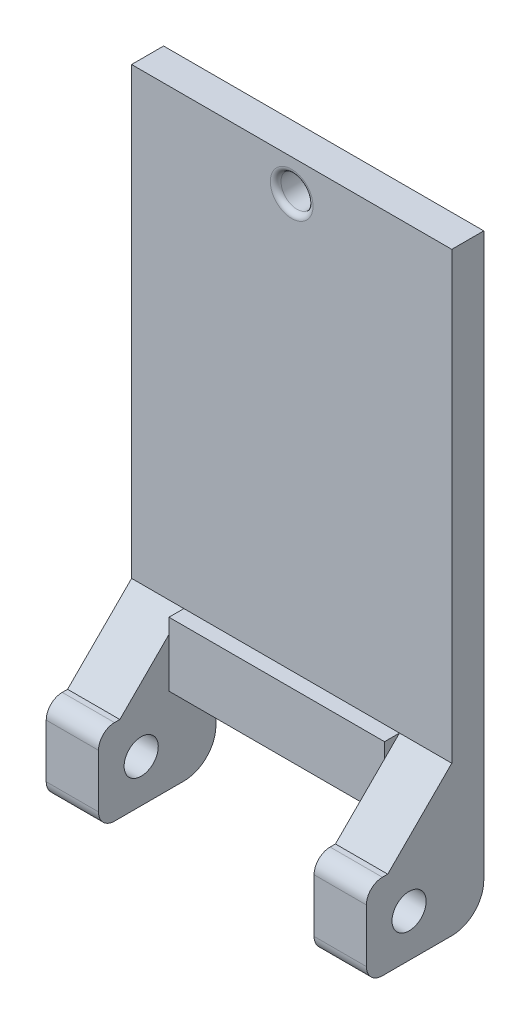
SolidWorks part; units mm, degrees
ref_plane "Front Plane" through (0, 0, 0) normal (0, 0, 1) x (1, 0, 0)
ref_plane "Top Plane" through (0, 0, 0) normal (0, 1, 0) x (1, 0, 0)
ref_plane "Right Plane" through (0, 0, 0) normal (1, 0, 0) x (0, 0, -1)
sketch "Sketch1" plane through (0, 0, 0) normal (0, 0, 1) x (1, 0, 0)
  line L1 (-15, -27.85) -> (15, -27.85)
  line L2 (-15, -27.85) -> (-15, 27.85)
  line L3 (-15, 27.85) -> (15, 27.85)
  line L4 (15, -27.85) -> (15, 27.85)
  line L5 (-15, -27.85) -> (15, 27.85) construction
  line L6 (-15, 27.85) -> (15, -27.85) construction
  point P0 (0, 0)
  dimension "D1" = 55.7
  dimension "D2" = 30
extrude "Boss-Extrude1" add sketch "Sketch1" along normal blind 3
sketch "Sketch2" plane through (0, 0, 3) normal (0, 0, 1) x (1, 0, 0)
  line L0 (0, -27.85) -> (0, 27.85) construction
  line L1 (15, 27.85) -> (-15, 27.85) construction
  line L3 (-15, -27.85) -> (-10.1, -27.85)
  line L4 (-15, -27.85) -> (-15, -19.85)
  line L5 (-15, -19.85) -> (-10.1, -19.85)
  line L6 (-10.1, -27.85) -> (-10.1, -19.85)
  point P6 (0, 0)
  dimension "D1" = 4.9
  dimension "D2" = 8
extrude "Boss-Extrude2" add sketch "Sketch2" along normal blind 8
sketch "Sketch3" plane through (-15, 0, 0) normal (-1, 0, 0) x (0, 0, 1)
  line L0 (11, -27.85) -> (0, -27.85) construction
  line L2 (3, 27.85) -> (3, -19.85) construction
  circle A0 centre (7, -23.85) radius 1.6
  dimension "D1" = 3.2
  dimension "D2" = 4
  dimension "D3" = 4
extrude "Cut-Extrude1" cut sketch "Sketch3" against normal through all
mirror "Mirror1" about plane through (0, 0, 0) normal (1, 0, 0) of "Cut-Extrude1", "Boss-Extrude2"
sketch "Sketch4" plane through (0, 0, 3) normal (0, 0, 1) x (1, 0, 0)
  line L1 (15, 27.85) -> (-15, 27.85) construction
  line L3 (0, 27.85) -> (0, 24.85) construction
  circle A0 centre (0, 24.85) radius 1.5
  dimension "D1" = 3
  dimension "D2" = 3
extrude "Cut-Extrude2" cut sketch "Sketch4" against normal blind 10 contours A0
fillet "Fillet3" radius 0.5 2 edges at (-1.5, 24.85, 0) (1.5, 24.85, 3)
fillet "Fillet4" radius 3 1 edges at (0, -27.85, 0)
sketch "Sketch5" plane through (0, 0, 3) normal (0, 0, 1) x (1, 0, 0)
  line L0 (10.1, -27.85) -> (10.1, -19.85) construction
  line L1 (-10.1, -27.85) -> (-10.1, -19.85) construction
  line L2 (10.1, -27.85) -> (10.1, -19.85)
  line L3 (-10.1, -27.85) -> (-10.1, -19.85)
  line L4 (-10.1, -19.85) -> (10.1, -19.85)
  line L5 (10.1, -27.85) -> (10.1, -30.3306)
  line L6 (10.1, -30.3306) -> (-10.1, -30.3306)
  line L7 (-10.1, -30.3306) -> (-10.1, -27.85)
  line M2 (-10.1, -19.85) -> (-10.1, -27.85)
  line M4 (10.1, -27.85) -> (10.1, -19.85)
extrude "Cut-Extrude4" cut sketch "Sketch5" against normal blind 10 and the other way through all contours L4 M2 M4 | L7 L6 L5 region at (0, -25.0903, 3)
fillet "Fillet5" radius 1.5 4 edges at (12.55, -27.85, 11) (12.55, -19.85, 11) (-12.55, -27.85, 11) (-12.55, -19.85, 11)
chamfer "Chamfer1" distance 6 angle 45 2 edges at (-12.55, -19.85, 3) (12.55, -19.85, 3)
sketch "Sketch6" plane through (0, 0, 3) normal (0, 0, 1) x (1, 0, 0)
  line L0 (-10.1, -13.85) -> (10.1, -13.85)
  line L1 (10.1, -19.85) -> (10.1, -13.85) construction
  line L2 (-10.1, -19.85) -> (10.1, -19.85) construction
  line L3 (-10.1, -13.85) -> (-10.1, -19.85) construction
  line L4 (10.1, -19.85) -> (10.1, -13.85)
  line L5 (-10.1, -19.85) -> (10.1, -19.85)
  line L6 (-10.1, -13.85) -> (-10.1, -19.85)
extrude "Boss-Extrude3" add sketch "Sketch6" along normal blind 1.4
